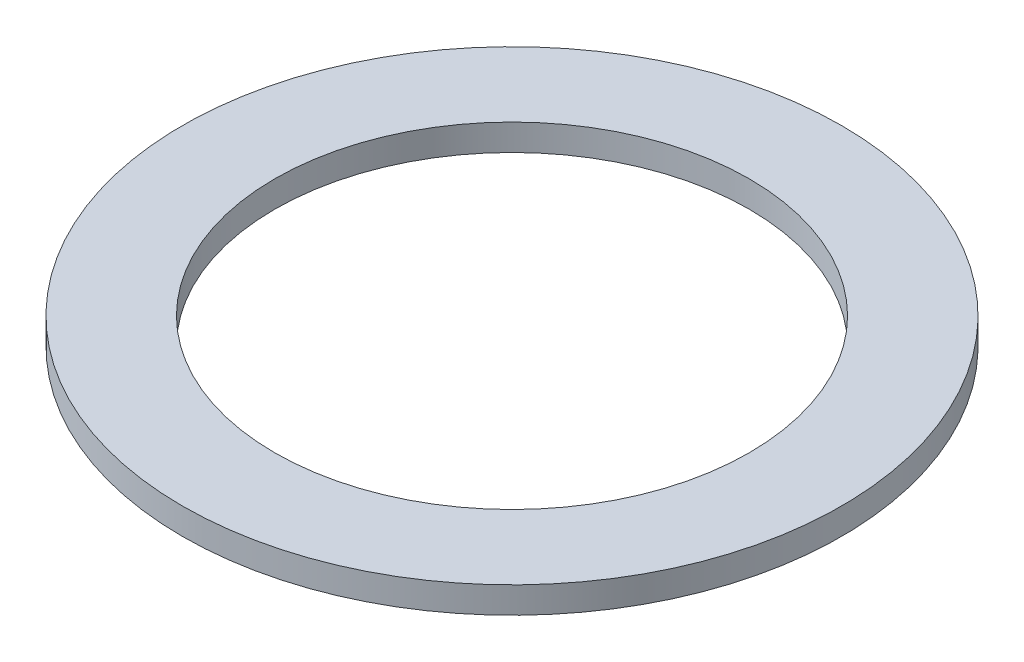
SolidWorks part; units mm, degrees
ref_plane "Front Plane" through (0, 0, 0) normal (0, 0, 1) x (1, 0, 0)
ref_plane "Top Plane" through (0, 0, 0) normal (0, 1, 0) x (1, 0, 0)
ref_plane "Right Plane" through (0, 0, 0) normal (1, 0, 0) x (0, 0, -1)
sketch "Sketch1" plane through (0, 0, 0) normal (0, 1, 0) x (1, 0, 0)
  line L0 (-12.5, 0) -> (12.5, 0) construction
  circle A0 centre (0, 0) radius 12.5 construction
  circle A1 centre (0, 0) radius 9 construction
  point P6 (-9, 0)
  point P7 (9, 0)
  point P8 (0, -12.5)
  point P9 (0, 12.5)
  dimension "OD" = 25
  dimension "ID" = 18
sketch "Sketch2" plane through (0, 0, 0) normal (1, 0, 0) x (0, 0, -1)
  line L1 (-12.5, 0.5) -> (12.5, 0.5) construction
  line L2 (-12.5, 0.5) -> (-12.5, -0.5) construction
  line L3 (-12.5, -0.5) -> (12.5, -0.5) construction
  line L4 (12.5, 0.5) -> (12.5, -0.5) construction
  dimension "Thickness" = 1
sketch "Sketch3" plane through (0, 0, 0) normal (0, 1, 0) x (1, 0, 0)
  circle A0 centre (0, 0) radius 12.5
  circle A1 centre (0, 0) radius 9
extrude "Boss-Extrude1" add sketch "Sketch3" along normal up to vertex (0.5 mm away) and the other way up to vertex (0.5 mm away) up to point (0, 0.5, -12.5) other way up to point (0, -0.5, -12.5)
